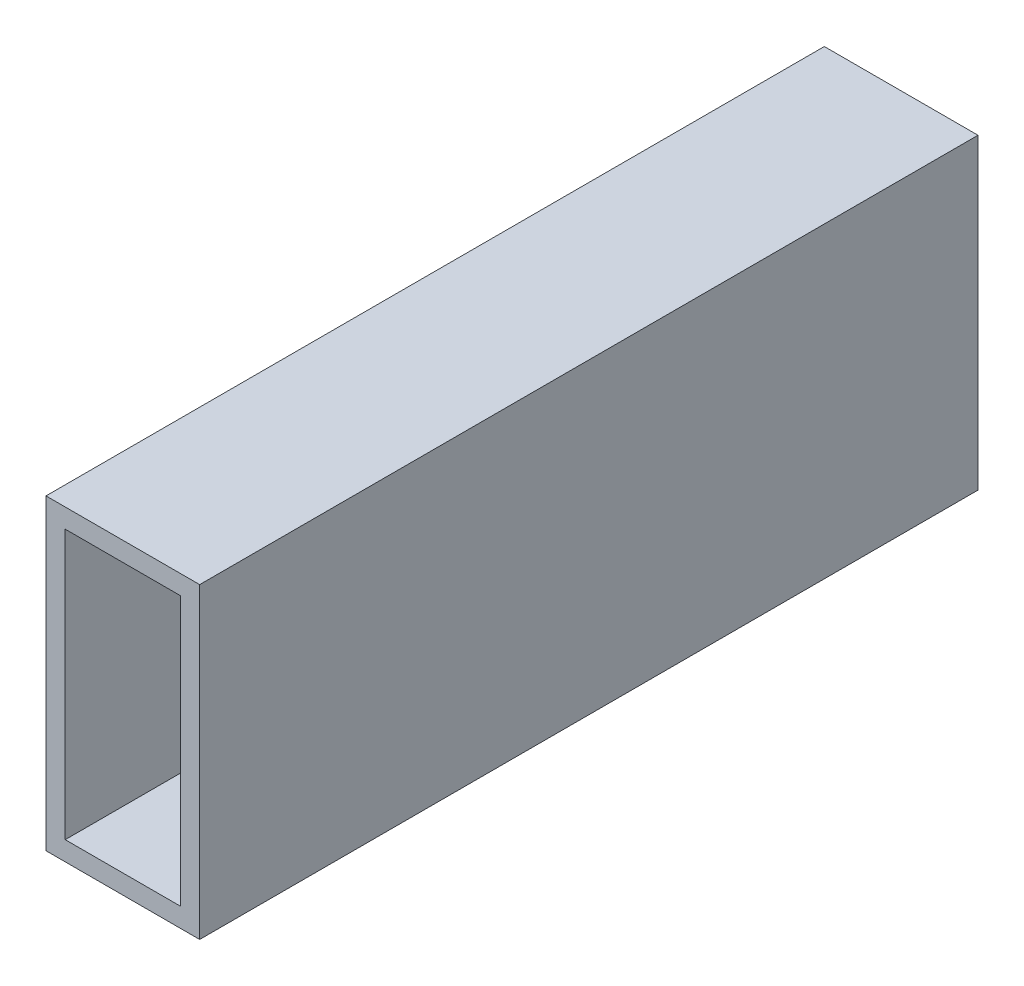
SolidWorks part; units mm, degrees
ref_plane "Front Plane" through (0, 0, 0) normal (0, 0, 1) x (1, 0, 0)
ref_plane "Top Plane" through (0, 0, 0) normal (0, 1, 0) x (1, 0, 0)
ref_plane "Right Plane" through (0, 0, 0) normal (1, 0, 0) x (0, 0, -1)
sketch "Sketch1" plane through (0, 0, 0) normal (0, 0, 1) x (1, 0, 0)
  line L0 (3.175, 47.625) -> (22.225, 47.625)
  line L1 (0, 0) -> (25.4, 0)
  line L2 (0, 0) -> (0, 50.8)
  line L3 (0, 50.8) -> (25.4, 50.8)
  line L4 (25.4, 0) -> (25.4, 50.8)
  line L5 (22.225, 3.175) -> (22.225, 47.625)
  line L6 (3.175, 3.175) -> (22.225, 3.175)
  line L7 (3.175, 3.175) -> (3.175, 47.625)
  dimension "D1" = 50.8
  dimension "D2" = 25.4
  dimension "D3" = 3.175
extrude "Boss-Extrude1" add sketch "Sketch1" along normal blind 128.651
